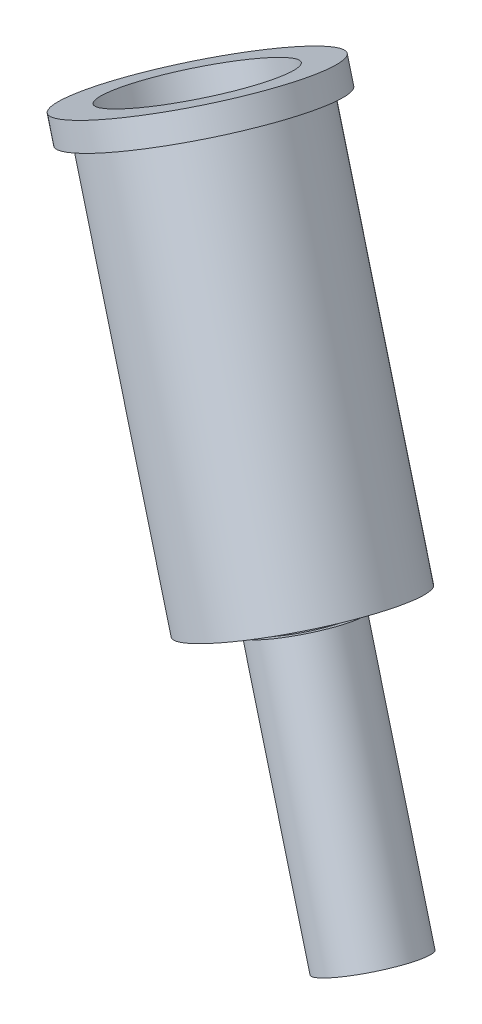
SolidWorks part; units mm, degrees
other "Markup1"
sketch "Sketch7" plane through (-206.0284, 201.4318, -3.7457) normal (-0.8382, 0.5448, -0.0267) x (0.4541, 0.7241, 0.5191)
ref_plane "Front Plane" through (0, 0, 0) normal (0, 0, 1) x (1, 0, 0)
ref_plane "Top Plane" through (0, 0, 0) normal (0, 1, 0) x (1, 0, 0)
ref_plane "Right Plane" through (0, 0, 0) normal (1, 0, 0) x (0, 0, -1)
sketch "Sketch1" plane through (-129.2035, 253.122, -50.2713) normal (-0.4477, 0.8771, -0.1742) x (0.8839, 0.4046, -0.2345)
  circle A0 centre (-31.0857, -28.5191) radius 11.43
  dimension "D1" = 22.86
extrude "Boss-Extrude1" add sketch "Sketch1" along normal blind 2.54 contours A0
sketch "Sketch2" plane through (-129.2035, 253.122, -50.2713) normal (0.4477, -0.8771, 0.1742) x (-0.8839, -0.4046, 0.2345)
  circle A0 centre (31.0857, -28.5191) radius 9.9949
  dimension "D1" = 19.9898
extrude "Boss-Extrude2" add sketch "Sketch2" along normal blind 38.1
sketch "Sketch3" plane through (-112.1466, 219.706, -43.6348) normal (0.4477, -0.8771, 0.1742) x (-0.8839, -0.4046, 0.2345)
  line L0 (33.4658, -38.4046) -> (28.7055, -18.6336) construction
  circle A0 centre (31.0857, -28.5191) radius 3.81
  dimension "D1" = 7.62
extrude "Boss-Extrude3" add sketch "Sketch3" along normal blind 1.016 contours A0
sketch "Sketch4" plane through (-111.6918, 218.8149, -43.4578) normal (0.4477, -0.8771, 0.1742) x (-0.8839, -0.4046, 0.2345)
  line L0 (39.2348, -26.557) -> (22.9365, -30.4812) construction
  circle A0 centre (31.0857, -28.5191) radius 4.7625
  dimension "D1" = 9.525
extrude "Boss-Extrude4" add sketch "Sketch4" along normal blind 26.0282 contours A0
sketch "Sketch5" plane through (-130.3406, 255.3497, -50.7138) normal (-0.4477, 0.8771, -0.1742) x (0.8839, 0.4046, -0.2345)
  line L0 (-33.4658, -38.4046) -> (-28.7055, -18.6336) construction
  circle A0 centre (-31.0857, -28.5191) radius 3.175
  dimension "D1" = 6.35
extrude "Cut-Extrude1" cut sketch "Sketch5" against normal through all
sketch "Sketch6" plane through (-130.3406, 255.3497, -50.7138) normal (-0.4477, 0.8771, -0.1742) x (0.8839, 0.4046, -0.2345)
  circle A0 centre (-31.0857, -28.5191) radius 7.9375
  dimension "D1" = 15.875
extrude "Cut-Extrude2" cut sketch "Sketch6" against normal blind 22.86
